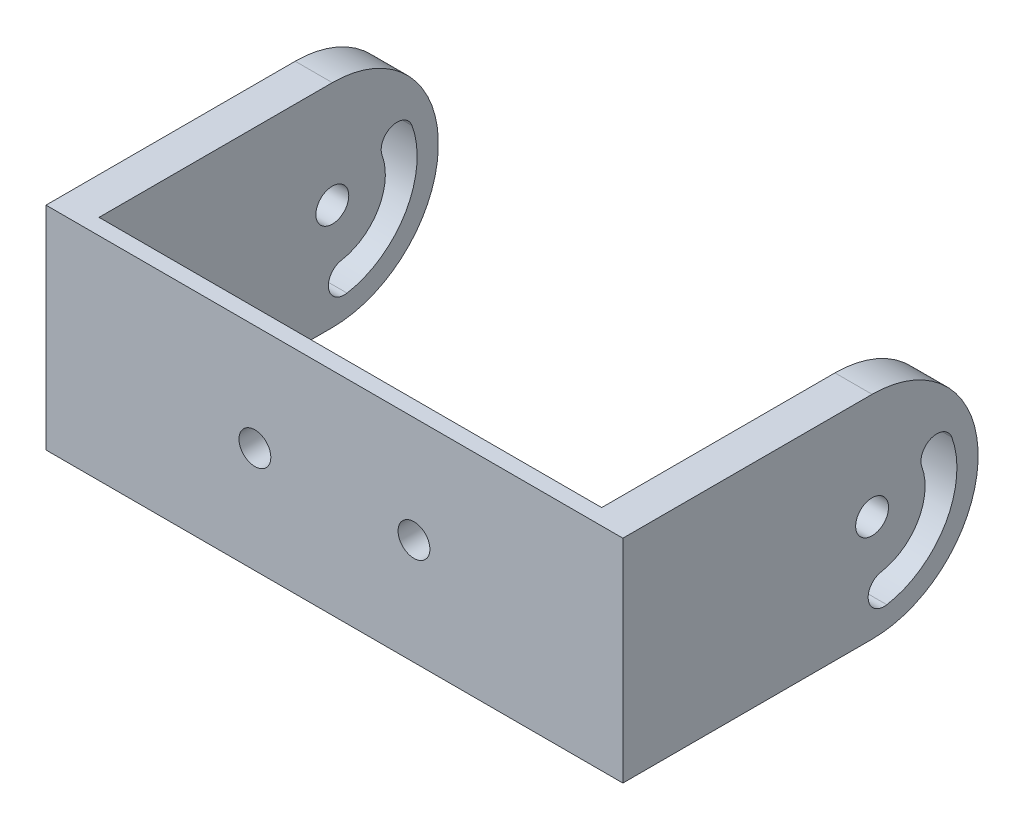
SolidWorks part; units mm, degrees
ref_plane "前视基准面" through (0, 0, 0) normal (0, 0, 1) x (1, 0, 0)
ref_plane "上视基准面" through (0, 0, 0) normal (0, 1, 0) x (1, 0, 0)
ref_plane "右视基准面" through (0, 0, 0) normal (1, 0, 0) x (0, 0, -1)
sketch "草图1" plane through (0, 0, 0) normal (0, 0, 1) x (1, 0, 0)
  line L1 (27.5, -15) -> (-26.9, -15)
  line L2 (27.5, -15) -> (27.5, 5)
  line L3 (27.5, 5) -> (-26.9, 5)
  line L4 (-26.9, -15) -> (-26.9, 5)
  point P0 (0, 0)
  dimension "D1" = 20
  dimension "D2" = 54.4
extrude "凸台-拉伸1" add sketch "草图1" along normal blind 3.5
ref_plane "基准面1" through (27.5, 0, 0) normal (1, 0, 0) x (0, 0, -1)
sketch "草图2" plane through (27.5, 0, 0) normal (1, 0, 0) x (0, 0, -1)
  line L0 (0, 5) -> (0, -15)
  line L1 (0, -15) -> (0, 5) construction
  line L2 (0, -15) -> (20, -15)
  line L4 (20, 5) -> (0, 5)
  line L5 (0, -5) -> (30, -5) construction
  line L6 (21.1287, -11.4013) -> (20, -5) construction
  line L7 (20, -5) -> (26.108, -2.7769) construction
  arc A0 (20, 5) -> (20, -15) centre (20, -5) cw
  circle A2 centre (20, -5) radius 1.55
  circle A3 centre (20, -5) radius 6.5 construction
  arc A16 (21.1287, -11.4013) -> (26.108, -2.7769) centre (20, -5) ccw construction
  arc A17 (21.3892, -12.8785) -> (27.5175, -2.2638) centre (20, -5) ccw
  arc A18 (20.8682, -9.924) -> (24.6985, -3.2899) centre (20, -5) ccw
  arc A19 (20.8682, -9.924) -> (21.3892, -12.8785) centre (21.1287, -11.4013) ccw
  arc A20 (27.5175, -2.2638) -> (24.6985, -3.2899) centre (26.108, -2.7769) ccw
  point P14 (25.6292, -8.25)
  dimension "D2" = 13
  dimension "D1" = 1.5
  dimension "D3" = 3.1
  dimension "D4" = 100
  dimension "D5" = 20
  dimension "D7" = 20
extrude "凸台-拉伸2" add sketch "草图2" against normal blind 3.5
ref_plane "基准面2" through (0.3, 0, 0) normal (-1, 0, 0) x (0, 0, 1)
mirror "镜向1" about plane through (0.3, 0, 0) normal (-1, 0, 0) of "凸台-拉伸2"
sketch "草图3" plane through (0, 0, 3.5) normal (0, 0, 1) x (1, 0, 0)
  line L1 (-26.9, 0) -> (27.5, 0) construction
  line L2 (27.5, 5) -> (-26.9, 5) construction
  line L4 (0.3, 0) -> (0.3, 5) construction
  circle A2 centre (7.8, -5) radius 1.5
  circle A4 centre (-7.2, -5) radius 1.5
  dimension "D1" = 15
  dimension "D3" = 3
  dimension "D5" = 10
extrude "切除-拉伸1" cut sketch "草图3" against normal blind 10
chamfer "倒角1" distance 2 angle 45 1 edges at (0.3, 5, 0)
